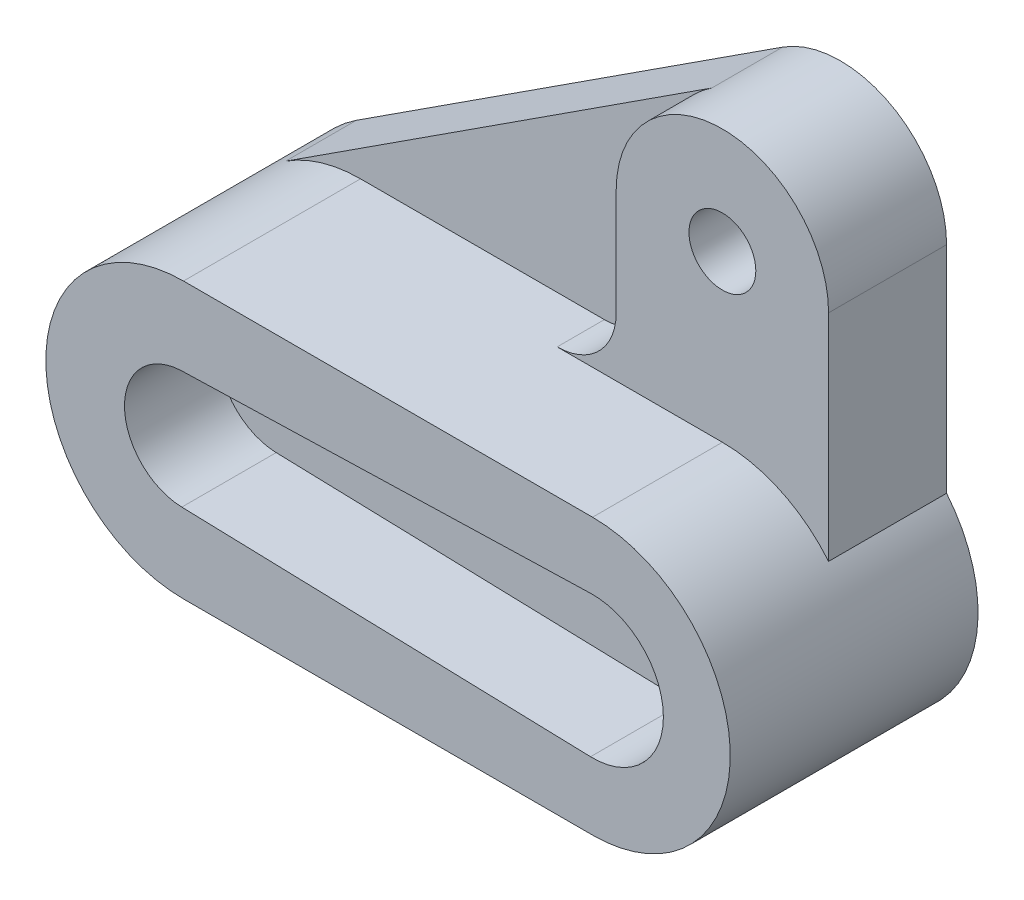
SolidWorks part; units mm, degrees
ref_plane "Front Plane" through (0, 0, 0) normal (0, 0, 1) x (1, 0, 0)
ref_plane "Top Plane" through (0, 0, 0) normal (0, 1, 0) x (1, 0, 0)
ref_plane "Right Plane" through (0, 0, 0) normal (1, 0, 0) x (0, 0, -1)
sketch "Sketch2" plane through (0, 0, 0) normal (0, 0, 1) x (1, 0, 0)
  line L0 (-58.2524, 35) -> (3.7476, 35)
  line L1 (45.2283, 17.9925) -> (-58.6851, 14.9938)
  line L2 (45.2283, -17.9925) -> (-58.6851, -14.9938)
  line L3 (-58.2524, -35) -> (45.7476, -35)
  line L4 (31.0537, 99.6515) -> (-77.3001, 29.363)
  line L5 (18.7476, 77) -> (18.7476, 50)
  line L6 (72.7476, 77) -> (72.7476, 22.2711)
  line L7 (3.7476, 35) -> (45.7476, 35)
  arc A0 (-58.6851, 14.9938) -> (-58.6851, -14.9938) centre (-58.2524, 0) ccw
  arc A1 (45.2283, -17.9925) -> (45.2283, 17.9925) centre (45.7476, 0) ccw
  arc A2 (-58.2524, 35) -> (-58.2524, -35) centre (-58.2524, 0) ccw
  arc A3 (45.7476, -35) -> (45.7476, 35) centre (45.7476, 0) ccw
  circle A4 centre (45.7476, 77) radius 8.5
  arc A5 (72.7476, 77) -> (18.7476, 77) centre (45.7476, 77) ccw
  arc A6 (3.7476, 35) -> (18.7476, 50) centre (3.7476, 50) ccw
  dimension "D1" = 15
extrude "Boss-Extrude3" add sketch "Sketch2" along normal blind 48 and the other way blind 15 contours A3 L7 L0 A2 L3 A1 L2 A0 L1 region at (-27.2524, 33.1245, 0)
extrude "Boss-Extrude4" add sketch "Sketch2<5>" along normal blind 24 contours L2 A1 L1 A0 region at (-2.7294, 0, 0)
sketch "Sketch2<5>" plane through (0, 0, 0) normal (0, 0, 1) x (1, 0, 0) same geometry as "Sketch2"
extrude "Boss-Extrude5" add sketch "Sketch2<6>" along normal blind 15 and the other way blind 15 contours A6 L7 A3 L6 A5 L5 A4 region at (45.952, 64.6757, 0)
sketch "Sketch2<6>" plane through (0, 0, 0) normal (0, 0, 1) x (1, 0, 0) same geometry as "Sketch2"
extrude "Boss-Extrude6" add sketch "Sketch2<7>" along normal blind 3 and the other way blind 15 contours L0 A6 L5 A5 L4 A2 region at (-10.6847, 54.6014, 0)
sketch "Sketch2<7>" plane through (0, 0, 0) normal (0, 0, 1) x (1, 0, 0) same geometry as "Sketch2"
